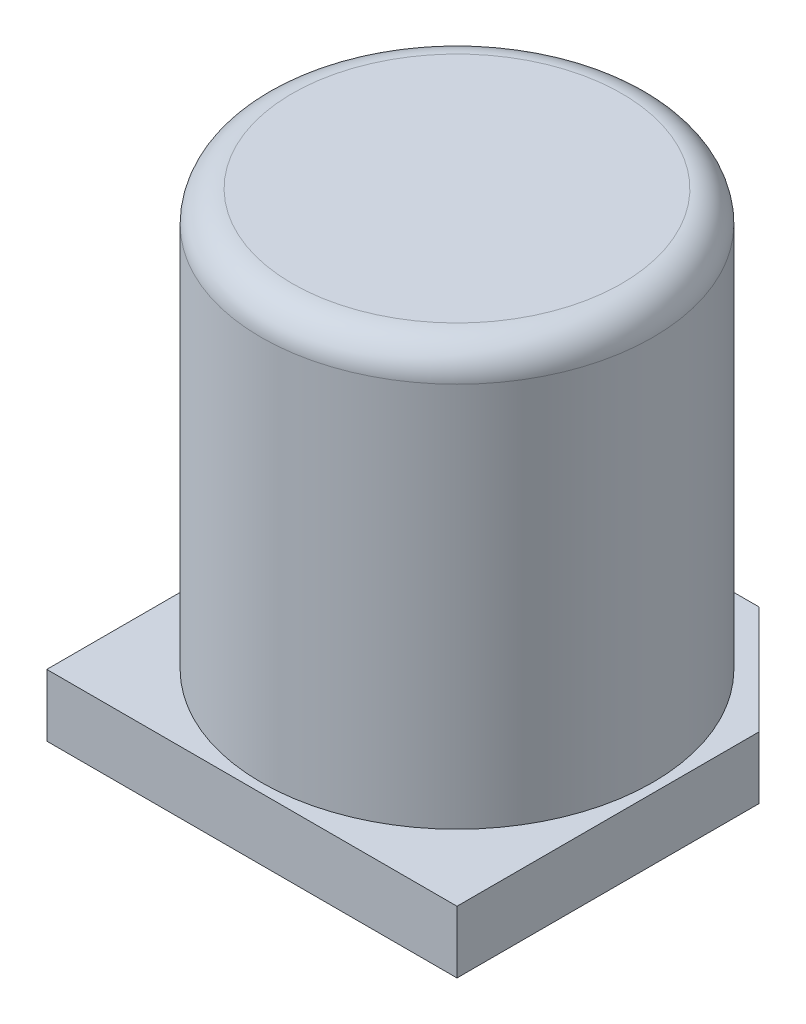
SolidWorks part; units mm, degrees
ref_plane "Plano frontal" through (0, 0, 0) normal (0, 0, 1) x (1, 0, 0)
ref_plane "Plano superior" through (0, 0, 0) normal (0, 1, 0) x (1, 0, 0)
ref_plane "Plano direito" through (0, 0, 0) normal (1, 0, 0) x (0, 0, -1)
ref_plane "Plano1" through (0, 0, 0) normal (0, -1, 0) x (1, 0, 0)
sketch "Esboço1" plane through (0, 0, 0) normal (0, -1, 0) x (1, 0, 0)
  line L0 (-3.3, 3.3) -> (-3.3, -3.3)
  line L1 (-3.3, -3.3) -> (3.3, -3.3)
  line L2 (3.3, -3.3) -> (3.3, 3.3)
  line L3 (3.3, 3.3) -> (-3.3, 3.3)
extrude "Ressalto-extrusão1" add sketch "Esboço1" against normal blind 1
sketch "Esboço2" plane through (0, 0, 0) normal (0, 0, 1) x (1, 0, 0)
  line L0 (3.15, 7.7) -> (0, 7.7)
  line L1 (0, 7.7) -> (0, 1)
  line L2 (0, 1) -> (3.15, 1)
  line L3 (3.15, 1) -> (3.15, 7.7)
  line L4 (0, 7.7) -> (0, 1) construction
revolve "Revolução1" add sketch "Esboço2" angle 360 about L4 reverse direction yes
chamfer "Chanfro1" distance 1.7375 angle 45 2 edges at (3.3, 0.5, -3.3) (-3.3, 0.5, -3.3)
fillet "Filete1" radius 0.5 1 edges at (0, 7.7, -3.15) tangent propagation no
